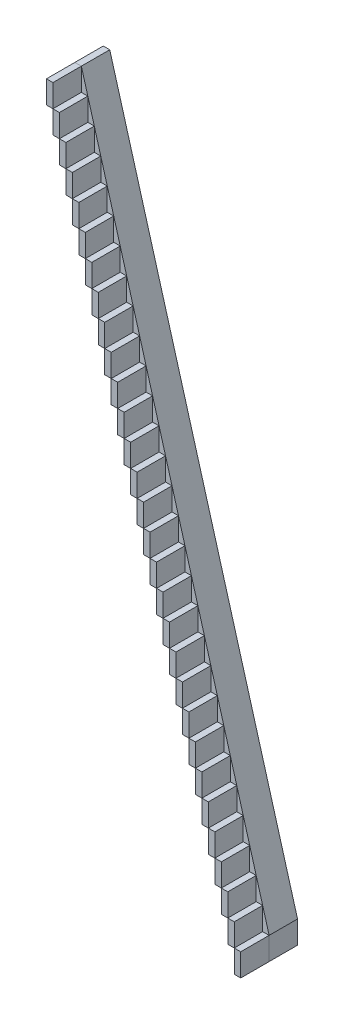
SolidWorks part; units mm, degrees
ref_plane "Front Plane" through (0, 0, 0) normal (0, 0, 1) x (1, 0, 0)
ref_plane "Top Plane" through (0, 0, 0) normal (0, 1, 0) x (1, 0, 0)
ref_plane "Right Plane" through (0, 0, 0) normal (1, 0, 0) x (0, 0, -1)
sketch "Sketch2" plane through (0, 0, 0) normal (0, 0, 1) x (1, 0, 0)
  line L0 (-2.1302, 0.1695) -> (-0.9902, 0.1695)
  line L1 (-0.9902, 0.1695) -> (-0.9902, 4.1695)
  line L3 (-2.1302, 4.1695) -> (-0.9902, 4.1695)
  line L5 (-2.1302, 0.1695) -> (-2.1302, 4.1695)
  line L124 (-3.2702, 4.1695) -> (-2.1302, 4.1695)
  line L125 (-2.1302, 4.1695) -> (-2.1302, 8.1695)
  line L129 (-3.2702, 4.1695) -> (-3.2702, 8.1695)
  line L244 (-3.2702, 8.1695) -> (-2.1302, 8.1695)
  line L248 (-4.4102, 8.1695) -> (-3.2702, 8.1695)
  line L249 (-3.2702, 8.1695) -> (-3.2702, 12.1695)
  line L250 (-4.4102, 8.1695) -> (-4.4102, 12.1695)
  line L368 (-4.4102, 12.1695) -> (-3.2702, 12.1695)
  line L372 (-5.5502, 12.1695) -> (-4.4102, 12.1695)
  line L373 (-4.4102, 12.1695) -> (-4.4102, 16.1695)
  line L374 (-5.5502, 12.1695) -> (-5.5502, 16.1695)
  line L492 (-5.5502, 16.1695) -> (-4.4102, 16.1695)
  line L496 (-6.6902, 16.1695) -> (-5.5502, 16.1695)
  line L497 (-5.5502, 16.1695) -> (-5.5502, 20.1695)
  line L498 (-6.6902, 16.1695) -> (-6.6902, 20.1695)
  line L616 (-6.6902, 20.1695) -> (-5.5502, 20.1695)
  line L620 (-7.8302, 20.1695) -> (-6.6902, 20.1695)
  line L621 (-6.6902, 20.1695) -> (-6.6902, 24.1695)
  line L622 (-7.8302, 20.1695) -> (-7.8302, 24.1695)
  line L740 (-7.8302, 24.1695) -> (-6.6902, 24.1695)
  line L744 (-8.9702, 24.1695) -> (-7.8302, 24.1695)
  line L745 (-7.8302, 24.1695) -> (-7.8302, 28.1695)
  line L746 (-8.9702, 24.1695) -> (-8.9702, 28.1695)
  line L864 (-8.9702, 28.1695) -> (-7.8302, 28.1695)
  line L868 (-10.1102, 28.1695) -> (-8.9702, 28.1695)
  line L869 (-8.9702, 28.1695) -> (-8.9702, 32.1695)
  line L870 (-10.1102, 28.1695) -> (-10.1102, 32.1695)
  line L988 (-10.1102, 32.1695) -> (-8.9702, 32.1695)
  line L992 (-11.2502, 32.1695) -> (-10.1102, 32.1695)
  line L993 (-10.1102, 32.1695) -> (-10.1102, 36.1695)
  line L994 (-11.2502, 32.1695) -> (-11.2502, 36.1695)
  line L1112 (-11.2502, 36.1695) -> (-10.1102, 36.1695)
  line L1116 (-12.3902, 36.1695) -> (-11.2502, 36.1695)
  line L1117 (-11.2502, 36.1695) -> (-11.2502, 40.1695)
  line L1118 (-12.3902, 36.1695) -> (-12.3902, 40.1695)
  line L1236 (-12.3902, 40.1695) -> (-11.2502, 40.1695)
  line L1240 (-13.5302, 40.1695) -> (-12.3902, 40.1695)
  line L1241 (-12.3902, 40.1695) -> (-12.3902, 44.1695)
  line L1242 (-13.5302, 40.1695) -> (-13.5302, 44.1695)
  line L1360 (-13.5302, 44.1695) -> (-12.3902, 44.1695)
  line L1364 (-14.6702, 44.1695) -> (-13.5302, 44.1695)
  line L1365 (-13.5302, 44.1695) -> (-13.5302, 48.1695)
  line L1366 (-14.6702, 44.1695) -> (-14.6702, 48.1695)
  line L1484 (-14.6702, 48.1695) -> (-13.5302, 48.1695)
  line L1488 (-15.8102, 48.1695) -> (-14.6702, 48.1695)
  line L1489 (-14.6702, 48.1695) -> (-14.6702, 52.1695)
  line L1490 (-15.8102, 48.1695) -> (-15.8102, 52.1695)
  line L1608 (-15.8102, 52.1695) -> (-14.6702, 52.1695)
  line L1612 (-16.9502, 52.1695) -> (-15.8102, 52.1695)
  line L1613 (-15.8102, 52.1695) -> (-15.8102, 56.1695)
  line L1614 (-16.9502, 52.1695) -> (-16.9502, 56.1695)
  line L1732 (-16.9502, 56.1695) -> (-15.8102, 56.1695)
  line L1736 (-18.0902, 56.1695) -> (-16.9502, 56.1695)
  line L1737 (-16.9502, 56.1695) -> (-16.9502, 60.1695)
  line L1738 (-18.0902, 56.1695) -> (-18.0902, 60.1695)
  line L1856 (-18.0902, 60.1695) -> (-16.9502, 60.1695)
  line L1860 (-19.2302, 60.1695) -> (-18.0902, 60.1695)
  line L1861 (-18.0902, 60.1695) -> (-18.0902, 64.1695)
  line L1862 (-19.2302, 60.1695) -> (-19.2302, 64.1695)
  line L1980 (-19.2302, 64.1695) -> (-18.0902, 64.1695)
  line L1984 (-20.3702, 64.1695) -> (-19.2302, 64.1695)
  line L1985 (-19.2302, 64.1695) -> (-19.2302, 68.1695)
  line L1986 (-20.3702, 64.1695) -> (-20.3702, 68.1695)
  line L2104 (-20.3702, 68.1695) -> (-19.2302, 68.1695)
  line L2108 (-21.5102, 68.1695) -> (-20.3702, 68.1695)
  line L2109 (-20.3702, 68.1695) -> (-20.3702, 72.1695)
  line L2110 (-21.5102, 68.1695) -> (-21.5102, 72.1695)
  line L2228 (-21.5102, 72.1695) -> (-20.3702, 72.1695)
  line L2232 (-22.6502, 72.1695) -> (-21.5102, 72.1695)
  line L2233 (-21.5102, 72.1695) -> (-21.5102, 76.1695)
  line L2234 (-22.6502, 72.1695) -> (-22.6502, 76.1695)
  line L2352 (-22.6502, 76.1695) -> (-21.5102, 76.1695)
  line L2356 (-23.7902, 76.1695) -> (-22.6502, 76.1695)
  line L2357 (-22.6502, 76.1695) -> (-22.6502, 80.1695)
  line L2358 (-23.7902, 76.1695) -> (-23.7902, 80.1695)
  line L2476 (-23.7902, 80.1695) -> (-22.6502, 80.1695)
  line L2480 (-24.9302, 80.1695) -> (-23.7902, 80.1695)
  line L2481 (-23.7902, 80.1695) -> (-23.7902, 84.1695)
  line L2482 (-24.9302, 80.1695) -> (-24.9302, 84.1695)
  line L2600 (-24.9302, 84.1695) -> (-23.7902, 84.1695)
  line L2604 (-26.0702, 84.1695) -> (-24.9302, 84.1695)
  line L2605 (-24.9302, 84.1695) -> (-24.9302, 88.1695)
  line L2606 (-26.0702, 84.1695) -> (-26.0702, 88.1695)
  line L2724 (-26.0702, 88.1695) -> (-24.9302, 88.1695)
  line L2728 (-27.2102, 88.1695) -> (-26.0702, 88.1695)
  line L2729 (-26.0702, 88.1695) -> (-26.0702, 92.1695)
  line L2730 (-27.2102, 88.1695) -> (-27.2102, 92.1695)
  line L2848 (-27.2102, 92.1695) -> (-26.0702, 92.1695)
  line L2852 (-28.3502, 92.1695) -> (-27.2102, 92.1695)
  line L2853 (-27.2102, 92.1695) -> (-27.2102, 96.1695)
  line L2854 (-28.3502, 92.1695) -> (-28.3502, 96.1695)
  line L2972 (-28.3502, 96.1695) -> (-27.2102, 96.1695)
  line L2976 (-29.4902, 96.1695) -> (-28.3502, 96.1695)
  line L2977 (-28.3502, 96.1695) -> (-28.3502, 100.1695)
  line L2978 (-29.4902, 96.1695) -> (-29.4902, 100.1695)
  line L3096 (-29.4902, 100.1695) -> (-28.3502, 100.1695)
  line L3100 (-30.6302, 100.1695) -> (-29.4902, 100.1695)
  line L3101 (-29.4902, 100.1695) -> (-29.4902, 104.1695)
  line L3102 (-30.6302, 100.1695) -> (-30.6302, 104.1695)
  line L3220 (-30.6302, 104.1695) -> (-29.4902, 104.1695)
  line L3224 (-31.7702, 104.1695) -> (-30.6302, 104.1695)
  line L3225 (-30.6302, 104.1695) -> (-30.6302, 108.1695)
  line L3226 (-31.7702, 104.1695) -> (-31.7702, 108.1695)
  line L3344 (-31.7702, 108.1695) -> (-30.6302, 108.1695)
  line L3348 (-32.9102, 108.1695) -> (-31.7702, 108.1695)
  line L3349 (-31.7702, 108.1695) -> (-31.7702, 112.1695)
  line L3350 (-32.9102, 108.1695) -> (-32.9102, 112.1695)
  line L3468 (-32.9102, 112.1695) -> (-31.7702, 112.1695)
  line L3472 (-34.0502, 112.1695) -> (-32.9102, 112.1695)
  line L3473 (-32.9102, 112.1695) -> (-32.9102, 116.1695)
  line L3474 (-34.0502, 112.1695) -> (-34.0502, 116.1695)
  line L3592 (-34.0502, 116.1695) -> (-32.9102, 116.1695)
  line L3596 (-35.1902, 116.1695) -> (-34.0502, 116.1695)
  line L3597 (-34.0502, 116.1695) -> (-34.0502, 120.1695)
  line L3598 (-35.1902, 116.1695) -> (-35.1902, 120.1695)
  line L3599 (-35.1902, 120.1695) -> (-34.0502, 120.1695)
  line L3682 (-2.1302, 112.1695) -> (-2.1302, 116.1695) [skipped]
  line L3683 (-2.1302, 112.1695) -> (-2.1302, 116.1695) [skipped]
  line L3684 (-0.9902, 112.1695) -> (-0.9902, 116.1695) [skipped]
  line L3713 (-2.1302, 116.1695) -> (-2.1302, 120.1695) [skipped]
  line L3714 (-2.1302, 116.1695) -> (-2.1302, 120.1695) [skipped]
  line L3715 (-0.9902, 116.1695) -> (-0.9902, 120.1695) [skipped]
  line L3768 (-2.1302, 108.1695) -> (-2.1302, 112.1695) [skipped]
  line L3769 (-2.1302, 108.1695) -> (-2.1302, 112.1695) [skipped]
  line L3770 (-0.9902, 108.1695) -> (-0.9902, 112.1695) [skipped]
  line L3821 (-2.1302, 104.1695) -> (-2.1302, 108.1695) [skipped]
  line L3822 (-2.1302, 104.1695) -> (-2.1302, 108.1695) [skipped]
  line L3823 (-0.9902, 104.1695) -> (-0.9902, 108.1695) [skipped]
  line L3872 (-2.1302, 100.1695) -> (-2.1302, 104.1695) [skipped]
  line L3873 (-2.1302, 100.1695) -> (-2.1302, 104.1695) [skipped]
  line L3874 (-2.1302, 100.1695) -> (-0.9902, 100.1695) [skipped]
  line L3875 (-2.1302, 100.1695) -> (-0.9902, 100.1695) [skipped]
  line L3876 (-0.9902, 96.1695) -> (-0.9902, 100.1695) [skipped]
  line L3923 (-2.1302, 96.1695) -> (-2.1302, 100.1695) [skipped]
  line L3924 (-2.1302, 96.1695) -> (-2.1302, 100.1695) [skipped]
  line L3947 (-0.9902, 92.1695) -> (-0.9902, 96.1695) [skipped]
  line L3988 (-2.1302, 92.1695) -> (-2.1302, 96.1695) [skipped]
  line L3989 (-2.1302, 92.1695) -> (-2.1302, 96.1695) [skipped]
  line L3990 (-3.2702, 92.1695) -> (-2.1302, 92.1695) [skipped]
  line L4062 (-2.1302, 88.1695) -> (-2.1302, 92.1695) [skipped]
  line L4063 (-2.1302, 88.1695) -> (-2.1302, 92.1695) [skipped]
  line L4068 (-2.1302, 84.1695) -> (-2.1302, 88.1695) [skipped]
  line L4069 (-2.1302, 84.1695) -> (-2.1302, 88.1695) [skipped]
  line L4070 (-0.9902, 84.1695) -> (-0.9902, 88.1695) [skipped]
  line L4071 (-0.9902, 80.1695) -> (-0.9902, 84.1695) [skipped]
  line L4072 (-2.1302, 80.1695) -> (-2.1302, 84.1695) [skipped]
  line L4073 (-2.1302, 80.1695) -> (-2.1302, 84.1695) [skipped]
  line L4150 (-2.1302, 60.1695) -> (-2.1302, 64.1695) [skipped]
  line L4151 (-2.1302, 60.1695) -> (-2.1302, 64.1695) [skipped]
  line L4152 (-0.9902, 60.1695) -> (-0.9902, 64.1695) [skipped]
  line L4153 (-0.9902, 64.1695) -> (-0.9902, 68.1695) [skipped]
  line L4154 (-2.1302, 64.1695) -> (-2.1302, 68.1695) [skipped]
  line L4155 (-2.1302, 64.1695) -> (-2.1302, 68.1695) [skipped]
  line L4210 (-2.1302, 68.1695) -> (-2.1302, 72.1695) [skipped]
  line L4211 (-2.1302, 68.1695) -> (-2.1302, 72.1695) [skipped]
  line L4212 (-0.9902, 68.1695) -> (-0.9902, 72.1695) [skipped]
  line L4213 (-0.9902, 72.1695) -> (-0.9902, 76.1695) [skipped]
  line L4214 (-2.1302, 72.1695) -> (-2.1302, 76.1695) [skipped]
  line L4215 (-2.1302, 72.1695) -> (-2.1302, 76.1695) [skipped]
  line L4278 (-2.1302, 76.1695) -> (-2.1302, 80.1695) [skipped]
  line L4279 (-2.1302, 76.1695) -> (-2.1302, 80.1695) [skipped]
  line L4280 (-0.9902, 76.1695) -> (-0.9902, 80.1695) [skipped]
  line L4317 (-2.1302, 36.1695) -> (-2.1302, 40.1695) [skipped]
  line L4318 (-2.1302, 36.1695) -> (-2.1302, 40.1695) [skipped]
  line L4319 (-0.9902, 36.1695) -> (-0.9902, 40.1695) [skipped]
  line L4320 (-0.9902, 40.1695) -> (-0.9902, 44.1695) [skipped]
  line L4321 (-2.1302, 40.1695) -> (-2.1302, 44.1695) [skipped]
  line L4322 (-2.1302, 40.1695) -> (-2.1302, 44.1695) [skipped]
  line L4353 (-2.1302, 44.1695) -> (-2.1302, 48.1695) [skipped]
  line L4354 (-2.1302, 44.1695) -> (-2.1302, 48.1695) [skipped]
  line L4355 (-0.9902, 44.1695) -> (-0.9902, 48.1695) [skipped]
  line L4356 (-0.9902, 48.1695) -> (-0.9902, 52.1695) [skipped]
  line L4357 (-2.1302, 48.1695) -> (-2.1302, 52.1695) [skipped]
  line L4358 (-2.1302, 48.1695) -> (-2.1302, 52.1695) [skipped]
  line L4397 (-2.1302, 52.1695) -> (-2.1302, 56.1695) [skipped]
  line L4398 (-2.1302, 52.1695) -> (-2.1302, 56.1695) [skipped]
  line L4399 (-0.9902, 52.1695) -> (-0.9902, 56.1695) [skipped]
  line L4400 (-0.9902, 56.1695) -> (-0.9902, 60.1695) [skipped]
  line L4401 (-2.1302, 56.1695) -> (-2.1302, 60.1695) [skipped]
  line L4402 (-2.1302, 56.1695) -> (-2.1302, 60.1695) [skipped]
  line L4450 (-3.2702, 12.1695) -> (-2.1302, 12.1695) [skipped]
  line L4451 (-2.1302, 8.1695) -> (-2.1302, 12.1695) [skipped]
  line L4452 (-2.1302, 8.1695) -> (-2.1302, 12.1695) [skipped]
  line L4453 (-2.1302, 8.1695) -> (-0.9902, 8.1695) [skipped]
  line L4454 (-2.1302, 12.1695) -> (-0.9902, 12.1695) [skipped]
  line L4455 (-2.1302, 12.1695) -> (-0.9902, 12.1695) [skipped]
  line L4456 (-2.1302, 16.1695) -> (-0.9902, 16.1695) [skipped]
  line L4457 (-2.1302, 16.1695) -> (-0.9902, 16.1695) [skipped]
  line L4458 (-2.1302, 20.1695) -> (-0.9902, 20.1695) [skipped]
  line L4459 (-2.1302, 20.1695) -> (-0.9902, 20.1695) [skipped]
  line L4460 (-2.1302, 24.1695) -> (-0.9902, 24.1695) [skipped]
  line L4461 (-2.1302, 24.1695) -> (-0.9902, 24.1695) [skipped]
  line L4462 (-2.1302, 28.1695) -> (-0.9902, 28.1695) [skipped]
  line L4463 (-2.1302, 28.1695) -> (-0.9902, 28.1695) [skipped]
  line L4464 (-2.1302, 32.1695) -> (-0.9902, 32.1695) [skipped]
  line L4465 (-2.1302, 32.1695) -> (-0.9902, 32.1695) [skipped]
  line L4466 (-2.1302, 36.1695) -> (-0.9902, 36.1695) [skipped]
  line L4467 (-2.1302, 36.1695) -> (-0.9902, 36.1695) [skipped]
  line L4469 (-3.2702, 36.1695) -> (-2.1302, 36.1695) [skipped]
  line L4488 (-2.1302, 28.1695) -> (-2.1302, 32.1695) [skipped]
  line L4489 (-2.1302, 28.1695) -> (-2.1302, 32.1695) [skipped]
  line L4490 (-0.9902, 28.1695) -> (-0.9902, 32.1695) [skipped]
  line L4506 (-3.2702, 20.1695) -> (-2.1302, 20.1695) [skipped]
  line L4507 (-2.1302, 16.1695) -> (-2.1302, 20.1695) [skipped]
  line L4508 (-2.1302, 16.1695) -> (-2.1302, 20.1695) [skipped]
  line L4509 (-2.1302, 20.1695) -> (-2.1302, 24.1695) [skipped]
  line L4510 (-2.1302, 20.1695) -> (-2.1302, 24.1695) [skipped]
  line L4511 (-0.9902, 4.1695) -> (-0.9902, 8.1695) [skipped]
  line L4512 (-2.1302, 8.1695) -> (-0.9902, 8.1695) [skipped]
  line L4513 (-3.2702, 0.1695) -> (-2.1302, 0.1695) [skipped]
  line L4514 (-3.2702, 0.1695) -> (-3.2702, 4.1695) [skipped]
  line L4515 (-3.2702, 0.1695) -> (-3.2702, 4.1695) [skipped]
  line L4516 (-4.4102, 0.1695) -> (-4.4102, 4.1695) [skipped]
  line L4517 (-4.4102, 0.1695) -> (-4.4102, 4.1695) [skipped]
  line L4518 (-5.5502, 0.1695) -> (-5.5502, 4.1695) [skipped]
  line L4519 (-5.5502, 0.1695) -> (-5.5502, 4.1695) [skipped]
  line L4520 (-6.6902, 0.1695) -> (-6.6902, 4.1695) [skipped]
  line L4521 (-6.6902, 0.1695) -> (-6.6902, 4.1695) [skipped]
  line L4522 (-7.8302, 0.1695) -> (-7.8302, 4.1695) [skipped]
  line L4523 (-7.8302, 0.1695) -> (-7.8302, 4.1695) [skipped]
  line L4524 (-8.9702, 0.1695) -> (-8.9702, 4.1695) [skipped]
  line L4525 (-8.9702, 0.1695) -> (-8.9702, 4.1695) [skipped]
  line L4526 (-10.1102, 0.1695) -> (-10.1102, 4.1695) [skipped]
  line L4527 (-10.1102, 0.1695) -> (-10.1102, 4.1695) [skipped]
  line L4528 (-11.2502, 0.1695) -> (-11.2502, 4.1695) [skipped]
  line L4529 (-11.2502, 0.1695) -> (-11.2502, 4.1695) [skipped]
  line L4530 (-12.3902, 0.1695) -> (-12.3902, 4.1695) [skipped]
  line L4531 (-12.3902, 0.1695) -> (-12.3902, 4.1695) [skipped]
  line L4532 (-13.5302, 0.1695) -> (-13.5302, 4.1695) [skipped]
  line L4533 (-13.5302, 0.1695) -> (-13.5302, 4.1695) [skipped]
  line L4534 (-14.6702, 0.1695) -> (-14.6702, 4.1695) [skipped]
  line L4535 (-14.6702, 0.1695) -> (-14.6702, 4.1695) [skipped]
  line L4536 (-15.8102, 0.1695) -> (-15.8102, 4.1695) [skipped]
  line L4537 (-15.8102, 0.1695) -> (-15.8102, 4.1695) [skipped]
  line L4538 (-16.9502, 0.1695) -> (-16.9502, 4.1695) [skipped]
  line L4539 (-16.9502, 0.1695) -> (-16.9502, 4.1695) [skipped]
  line L4540 (-18.0902, 0.1695) -> (-18.0902, 4.1695) [skipped]
  line L4541 (-18.0902, 0.1695) -> (-18.0902, 4.1695) [skipped]
  line L4542 (-19.2302, 0.1695) -> (-19.2302, 4.1695) [skipped]
  line L4543 (-19.2302, 0.1695) -> (-19.2302, 4.1695) [skipped]
  line L4544 (-20.3702, 0.1695) -> (-20.3702, 4.1695) [skipped]
  line L4545 (-20.3701, 0.1695) -> (-20.3701, 4.1695) [skipped]
  line L4546 (-21.5101, 0.1695) -> (-21.5101, 4.1695) [skipped]
  line L4547 (-21.5101, 0.1695) -> (-21.5101, 4.1695) [skipped]
  line L4548 (-22.6501, 0.1695) -> (-22.6501, 4.1695) [skipped]
  line L4549 (-22.6501, 0.1695) -> (-22.6501, 4.1695) [skipped]
  line L4550 (-23.7901, 0.1695) -> (-23.7901, 4.1695) [skipped]
  line L4551 (-23.7901, 0.1695) -> (-23.7901, 4.1695) [skipped]
  line L4552 (-24.9301, 0.1695) -> (-24.9301, 4.1695) [skipped]
  line L4553 (-24.9301, 0.1695) -> (-24.9301, 4.1695) [skipped]
  line L4554 (-26.0701, 0.1695) -> (-26.0701, 4.1695) [skipped]
  line L4555 (-26.0701, 0.1695) -> (-26.0701, 4.1695) [skipped]
  line L4556 (-27.2101, 0.1695) -> (-27.2101, 4.1695) [skipped]
  line L4557 (-27.2101, 0.1695) -> (-27.2101, 4.1695) [skipped]
  line L4558 (-28.3501, 0.1695) -> (-28.3501, 4.1695) [skipped]
  line L4559 (-28.3501, 0.1695) -> (-28.3501, 4.1695) [skipped]
  line L4560 (-29.4901, 0.1695) -> (-29.4901, 4.1695) [skipped]
  line L4561 (-29.4901, 0.1695) -> (-29.4901, 4.1695) [skipped]
  line L4562 (-30.6301, 0.1695) -> (-30.6301, 4.1695) [skipped]
  line L4563 (-30.6301, 0.1695) -> (-30.6301, 4.1695) [skipped]
  line L4564 (-31.7701, 0.1695) -> (-31.7701, 4.1695) [skipped]
  line L4565 (-31.7701, 0.1695) -> (-31.7701, 4.1695) [skipped]
  line L4566 (-32.9101, 0.1695) -> (-32.9101, 4.1695) [skipped]
  line L4567 (-32.9101, 0.1695) -> (-32.9101, 4.1695) [skipped]
  line L4568 (-34.0501, 0.1695) -> (-34.0501, 4.1695) [skipped]
  line L4569 (-34.0501, 0.1695) -> (-34.0501, 4.1695) [skipped]
  line L4570 (-35.1901, 0.1695) -> (-35.1901, 4.1695) [skipped]
  line L4571 (-4.4102, 0.1695) -> (-3.2702, 0.1695) [skipped]
  line L4586 (-18.0902, 0.1695) -> (-16.9502, 0.1695) [skipped]
  line L4587 (-18.0902, 4.1695) -> (-16.9502, 4.1695) [skipped]
  line L4588 (-19.2302, 0.1695) -> (-18.0902, 0.1695) [skipped]
  line L4589 (-19.2302, 4.1695) -> (-18.0902, 4.1695) [skipped]
  line L4590 (-20.3702, 0.1695) -> (-19.2302, 0.1695) [skipped]
  line L4591 (-20.3702, 4.1695) -> (-19.2302, 4.1695) [skipped]
  line L4592 (-21.5101, 0.1695) -> (-20.3701, 0.1695) [skipped]
  line L4593 (-21.5101, 4.1695) -> (-20.3701, 4.1695) [skipped]
  line L4594 (-22.6501, 0.1695) -> (-21.5101, 0.1695) [skipped]
  line L4595 (-22.6501, 4.1695) -> (-21.5101, 4.1695) [skipped]
  line L4596 (-23.7901, 0.1695) -> (-22.6501, 0.1695) [skipped]
  line L4597 (-23.7901, 4.1695) -> (-22.6501, 4.1695) [skipped]
  line L4598 (-24.9301, 0.1695) -> (-23.7901, 0.1695) [skipped]
  line L4599 (-24.9301, 4.1695) -> (-23.7901, 4.1695) [skipped]
  line L4600 (-26.0701, 0.1695) -> (-24.9301, 0.1695) [skipped]
  line L4601 (-26.0701, 4.1695) -> (-24.9301, 4.1695) [skipped]
  line L4602 (-27.2101, 0.1695) -> (-26.0701, 0.1695) [skipped]
  line L4603 (-27.2101, 4.1695) -> (-26.0701, 4.1695) [skipped]
  line L4604 (-28.3501, 0.1695) -> (-27.2101, 0.1695) [skipped]
  line L4605 (-28.3501, 4.1695) -> (-27.2101, 4.1695) [skipped]
  line L4606 (-29.4901, 0.1695) -> (-28.3501, 0.1695) [skipped]
  line L4607 (-29.4901, 4.1695) -> (-28.3501, 4.1695) [skipped]
  line L4608 (-30.6301, 0.1695) -> (-29.4901, 0.1695) [skipped]
  line L4609 (-30.6301, 4.1695) -> (-29.4901, 4.1695) [skipped]
  line L4610 (-31.7701, 0.1695) -> (-30.6301, 0.1695) [skipped]
  line L4611 (-31.7701, 4.1695) -> (-30.6301, 4.1695) [skipped]
  line L4612 (-32.9101, 0.1695) -> (-31.7701, 0.1695) [skipped]
  line L4613 (-32.9101, 4.1695) -> (-31.7701, 4.1695) [skipped]
  line L4614 (-34.0501, 0.1695) -> (-32.9101, 0.1695) [skipped]
  line L4615 (-34.0501, 4.1695) -> (-32.9101, 4.1695) [skipped]
  line L4616 (-35.1901, 0.1695) -> (-34.0501, 0.1695) [skipped]
  line L4617 (-35.1901, 4.1695) -> (-34.0501, 4.1695) [skipped]
  line L4638 (-2.1302, 120.1695) -> (-0.9902, 120.1695) [skipped]
  line L4639 (-3.2702, 120.1695) -> (-2.1302, 120.1695) [skipped]
  line L4652 (-2.1302, 116.1695) -> (-0.9902, 116.1695) [skipped]
  line L4653 (-3.2702, 116.1695) -> (-2.1302, 116.1695) [skipped]
  line L4666 (-2.1302, 116.1695) -> (-0.9902, 116.1695) [skipped]
  line L4678 (-2.1302, 112.1695) -> (-0.9902, 112.1695) [skipped]
  line L4679 (-3.2702, 112.1695) -> (-2.1302, 112.1695) [skipped]
  line L4692 (-2.1302, 112.1695) -> (-0.9902, 112.1695) [skipped]
  line L4704 (-2.1302, 108.1695) -> (-0.9902, 108.1695) [skipped]
  line L4705 (-3.2702, 108.1695) -> (-2.1302, 108.1695) [skipped]
  line L4718 (-2.1302, 108.1695) -> (-0.9902, 108.1695) [skipped]
  line L4730 (-2.1302, 104.1695) -> (-0.9902, 104.1695) [skipped]
  line L4731 (-3.2702, 104.1695) -> (-2.1302, 104.1695) [skipped]
  line L4744 (-2.1302, 104.1695) -> (-0.9902, 104.1695) [skipped]
  line L4756 (-3.2702, 100.1695) -> (-2.1302, 100.1695) [skipped]
  line L4780 (-0.9902, 100.1695) -> (-0.9902, 104.1695) [skipped]
  line L4781 (-2.1302, 96.1695) -> (-0.9902, 96.1695) [skipped]
  line L4782 (-3.2702, 96.1695) -> (-2.1302, 96.1695) [skipped]
  line L4795 (-2.1302, 96.1695) -> (-0.9902, 96.1695) [skipped]
  line L4807 (-2.1302, 92.1695) -> (-0.9902, 92.1695) [skipped]
  line L4820 (-2.1302, 92.1695) -> (-0.9902, 92.1695) [skipped]
  line L4832 (-2.1302, 88.1695) -> (-0.9902, 88.1695) [skipped]
  line L4833 (-3.2702, 88.1695) -> (-2.1302, 88.1695) [skipped]
  line L4844 (-2.1302, 88.1695) -> (-0.9902, 88.1695) [skipped]
  line L4855 (-0.9902, 88.1695) -> (-0.9902, 92.1695) [skipped]
  line L4856 (-2.1302, 84.1695) -> (-0.9902, 84.1695) [skipped]
  line L4857 (-3.2702, 84.1695) -> (-2.1302, 84.1695) [skipped]
  line L4870 (-2.1302, 84.1695) -> (-0.9902, 84.1695) [skipped]
  line L4882 (-2.1302, 80.1695) -> (-0.9902, 80.1695) [skipped]
  line L4883 (-3.2702, 80.1695) -> (-2.1302, 80.1695) [skipped]
  line L4896 (-2.1302, 80.1695) -> (-0.9902, 80.1695) [skipped]
  line L4908 (-2.1302, 76.1695) -> (-0.9902, 76.1695) [skipped]
  line L4909 (-3.2702, 76.1695) -> (-2.1302, 76.1695) [skipped]
  line L4922 (-2.1302, 76.1695) -> (-0.9902, 76.1695) [skipped]
  line L4994 (-2.1302, 48.1695) -> (-0.9902, 48.1695) [skipped]
  line L4995 (-3.2702, 48.1695) -> (-2.1302, 48.1695) [skipped]
  line L5004 (-2.1302, 48.1695) -> (-0.9902, 48.1695) [skipped]
  line L5012 (-2.1302, 44.1695) -> (-0.9902, 44.1695) [skipped]
  line L5013 (-3.2702, 44.1695) -> (-2.1302, 44.1695) [skipped]
  line L5021 (-2.1302, 44.1695) -> (-0.9902, 44.1695) [skipped]
  line L5028 (-2.1302, 40.1695) -> (-0.9902, 40.1695) [skipped]
  line L5029 (-3.2702, 40.1695) -> (-2.1302, 40.1695) [skipped]
  line L5036 (-2.1302, 40.1695) -> (-0.9902, 40.1695) [skipped]
  line L5051 (-3.2702, 32.1695) -> (-2.1302, 32.1695) [skipped]
  line L5057 (-3.2702, 28.1695) -> (-2.1302, 28.1695) [skipped]
  line L5062 (-3.2702, 24.1695) -> (-2.1302, 24.1695) [skipped]
  line L5066 (-0.9902, 20.1695) -> (-0.9902, 24.1695) [skipped]
  line L5067 (-0.9902, 24.1695) -> (-0.9902, 28.1695) [skipped]
  line L5068 (-2.1302, 24.1695) -> (-2.1302, 28.1695) [skipped]
  line L5069 (-2.1302, 24.1695) -> (-2.1302, 28.1695) [skipped]
  line L5070 (-0.9902, 32.1695) -> (-0.9902, 36.1695) [skipped]
  line L5071 (-2.1302, 32.1695) -> (-2.1302, 36.1695) [skipped]
  line L5072 (-2.1302, 32.1695) -> (-2.1302, 36.1695) [skipped]
  line L5073 (-8.9702, 0.1695) -> (-7.8302, 0.1695) [skipped]
  line L5074 (-8.9702, 4.1695) -> (-7.8302, 4.1695) [skipped]
  line L5075 (-10.1102, 0.1695) -> (-8.9702, 0.1695) [skipped]
  line L5076 (-10.1102, 4.1695) -> (-8.9702, 4.1695) [skipped]
  line L5077 (-11.2502, 0.1695) -> (-10.1102, 0.1695) [skipped]
  line L5078 (-11.2502, 4.1695) -> (-10.1102, 4.1695) [skipped]
  line L5079 (-12.3902, 0.1695) -> (-11.2502, 0.1695) [skipped]
  line L5080 (-12.3902, 4.1695) -> (-11.2502, 4.1695) [skipped]
  line L5081 (-13.5302, 0.1695) -> (-12.3902, 0.1695) [skipped]
  line L5082 (-13.5302, 4.1695) -> (-12.3902, 4.1695) [skipped]
  line L5083 (-14.6702, 0.1695) -> (-13.5302, 0.1695) [skipped]
  line L5084 (-14.6702, 4.1695) -> (-13.5302, 4.1695) [skipped]
  line L5085 (-15.8102, 0.1695) -> (-14.6702, 0.1695) [skipped]
  line L5086 (-15.8102, 4.1695) -> (-14.6702, 4.1695) [skipped]
  line L5087 (-16.9502, 0.1695) -> (-15.8102, 0.1695) [skipped]
  line L5088 (-16.9502, 4.1695) -> (-15.8102, 4.1695) [skipped]
  line L5089 (-7.8302, 0.1695) -> (-6.6902, 0.1695) [skipped]
  line L5090 (-7.8302, 4.1695) -> (-6.6902, 4.1695) [skipped]
  line L5091 (-4.4102, 4.1695) -> (-3.2702, 4.1695) [skipped]
  line L5092 (-5.5502, 4.1695) -> (-4.4102, 4.1695) [skipped]
  line L5093 (-6.6902, 4.1695) -> (-5.5502, 4.1695) [skipped]
  line L5097 (-5.5502, 0.1695) -> (-4.4102, 0.1695) [skipped]
  line L5098 (-6.6902, 0.1695) -> (-5.5502, 0.1695) [skipped]
  line L5099 (-0.9902, 8.1695) -> (-0.9902, 12.1695) [skipped]
  line L5100 (-0.9902, 12.1695) -> (-0.9902, 16.1695) [skipped]
  line L5101 (-0.9902, 16.1695) -> (-0.9902, 20.1695) [skipped]
  line L5102 (-2.1302, 12.1695) -> (-2.1302, 16.1695) [skipped]
  line L5103 (-2.1302, 12.1695) -> (-2.1302, 16.1695) [skipped]
  line L5104 (-3.2702, 16.1695) -> (-2.1302, 16.1695) [skipped]
  line L5105 (-2.1302, 52.1695) -> (-0.9902, 52.1695) [skipped]
  line L5106 (-3.2702, 52.1695) -> (-2.1302, 52.1695) [skipped]
  line L5107 (-2.1302, 52.1695) -> (-0.9902, 52.1695) [skipped]
  line L5108 (-2.1302, 56.1695) -> (-0.9902, 56.1695) [skipped]
  line L5109 (-3.2702, 56.1695) -> (-2.1302, 56.1695) [skipped]
  line L5110 (-2.1302, 56.1695) -> (-0.9902, 56.1695) [skipped]
  line L5111 (-2.1302, 60.1695) -> (-0.9902, 60.1695) [skipped]
  line L5112 (-3.2702, 60.1695) -> (-2.1302, 60.1695) [skipped]
  line L5113 (-2.1302, 60.1695) -> (-0.9902, 60.1695) [skipped]
  line L5114 (-2.1302, 64.1695) -> (-0.9902, 64.1695) [skipped]
  line L5115 (-3.2702, 64.1695) -> (-2.1302, 64.1695) [skipped]
  line L5116 (-2.1302, 64.1695) -> (-0.9902, 64.1695) [skipped]
  line L5117 (-2.1302, 68.1695) -> (-0.9902, 68.1695) [skipped]
  line L5118 (-3.2702, 68.1695) -> (-2.1302, 68.1695) [skipped]
  line L5119 (-2.1302, 68.1695) -> (-0.9902, 68.1695) [skipped]
  line L5120 (-2.1302, 72.1695) -> (-0.9902, 72.1695) [skipped]
  line L5121 (-3.2702, 72.1695) -> (-2.1302, 72.1695) [skipped]
  line L5122 (-2.1302, 72.1695) -> (-0.9902, 72.1695) [skipped]
  line L5123 (-3.2702, 4.1695) -> (-2.1302, 4.1695) [skipped]
  line L5124 (-2.1302, 4.1695) -> (-0.9902, 4.1695) [skipped]
  point P2 (0, 0)
  point P5 (0, 0)
  point P10 (0, 0)
  point P11 (0, 0)
  dimension "D2" = 4
  dimension "D3" = 30
  dimension "D4" = 30
extrude "Boss-Extrude1" add sketch "Sketch2" along normal blind 5
sketch "Sketch3" plane through (0, 0, 0) normal (0, 0, -1) x (-1, 0, 0)
  line L0 (0.9902, 4.1695) -> (34.0502, 120.1695)
  line L1 (34.0502, 120.1695) -> (35.1902, 120.1695)
  line L2 (35.1902, 120.1695) -> (35.1902, 116.1695)
  line L3 (35.1902, 116.1695) -> (2.1302, 0.1695)
  line L4 (2.1302, 0.1695) -> (0.9902, 0.1695)
  line L5 (0.9902, 0.1695) -> (0.9902, 4.1695)
extrude "Boss-Extrude3" add sketch "Sketch3" along normal blind 5 separate body
